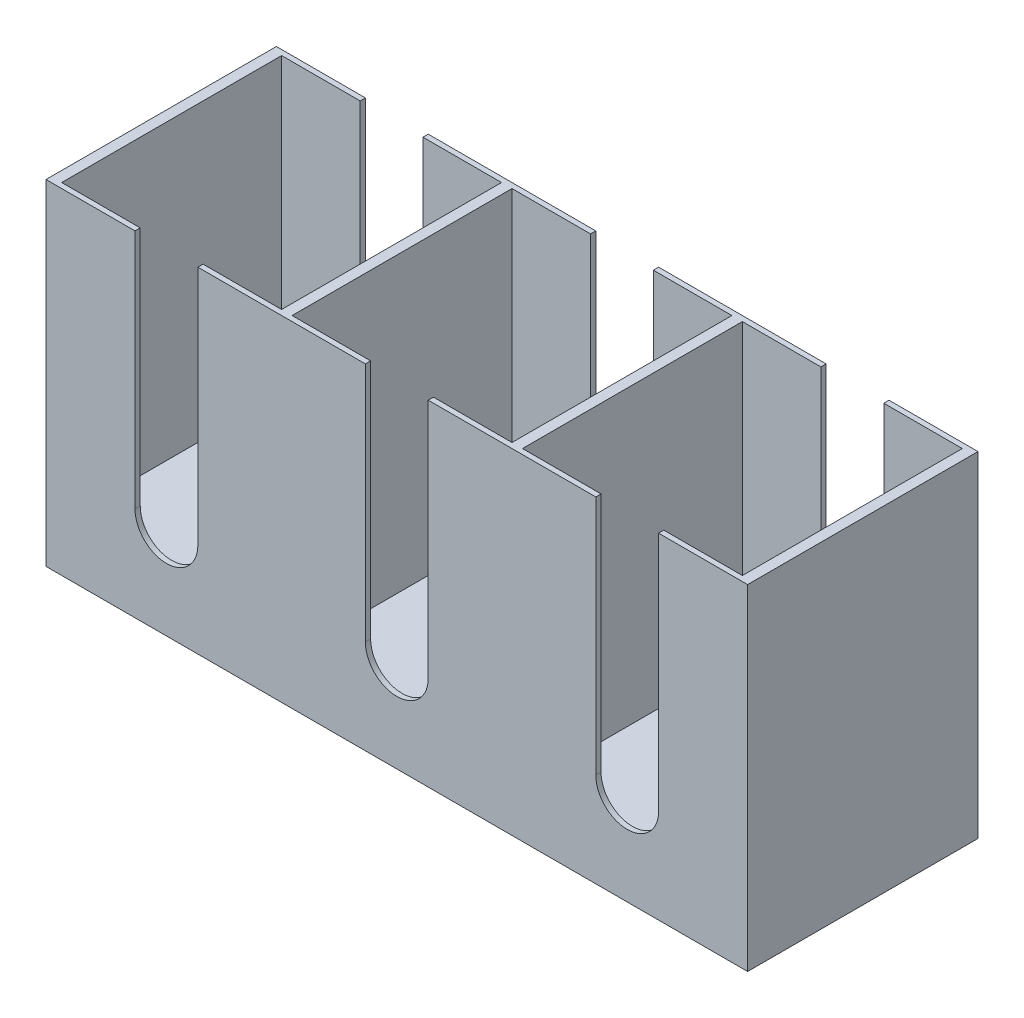
SolidWorks part; units mm, degrees
material "ABS"
ref_plane "Alzado" through (0, 0, 0) normal (0, 0, 1) x (1, 0, 0)
ref_plane "Planta" through (0, 0, 0) normal (0, 1, 0) x (1, 0, 0)
ref_plane "Vista lateral" through (0, 0, 0) normal (1, 0, 0) x (0, 0, -1)
sketch "Croquis1" plane through (0, 0, 0) normal (0, 1, 0) x (1, 0, 0)
  line L0 (-10.5, 10.5) -> (10.5, 10.5)
  line L1 (-33.5, 11) -> (33.5, 11)
  line L2 (-33.5, 11) -> (-33.5, -11)
  line L3 (-33.5, -11) -> (33.5, -11)
  line L4 (33.5, 11) -> (33.5, -11)
  line L5 (-33.5, 11) -> (33.5, -11) construction
  line L6 (-33.5, -11) -> (33.5, 11) construction
  line L11 (-10.5, 10.5) -> (-10.5, -10.5)
  line L12 (10.5, 10.5) -> (10.5, -10.5)
  line L13 (-32.5, 10.5) -> (-11.5, 10.5)
  line L14 (-32.5, 10.5) -> (-32.5, -10.5)
  line L15 (-32.5, -10.5) -> (-11.5, -10.5)
  line L16 (-11.5, 10.5) -> (-11.5, -10.5)
  line L17 (-32.5, 10.5) -> (-11.5, -10.5) construction
  line L18 (-32.5, -10.5) -> (-11.5, 10.5) construction
  line L19 (-10.5, -10.5) -> (10.5, -10.5)
  line L20 (11.5, 10.5) -> (32.5, 10.5)
  line L21 (11.5, 10.5) -> (11.5, -10.5)
  line L22 (32.5, 10.5) -> (32.5, -10.5)
  line L23 (11.5, -10.5) -> (32.5, -10.5)
  point P0 (0, 0)
  point P5 (0, 0)
  point P13 (-22, 0)
  dimension "D1" = 22
  dimension "D2" = 67
  dimension "D3" = 3
  dimension "D4" = 21
  dimension "D5" = 1
  dimension "D6" = 1
extrude "Saliente-Extruir1" add sketch "Croquis1" along normal blind 32
extrude "Saliente-Extruir2" add sketch "Croquis1<2>" along normal blind 4 contours L11 L19 L12 L0 | L16 L13 L14 L15 | L21 L23 L22 L20 region at (0, 0, 0) region at (-22, 0, 0) region at (22, 0, 0)
sketch "Croquis1<2>" plane through (0, 0, 0) normal (0, 1, 0) x (1, 0, 0) same geometry as "Croquis1"
sketch "Croquis2" plane through (0, 0, 11) normal (0, 0, 1) x (1, 0, 0)
  line L0 (-25, 32) -> (-25, 9)
  line L1 (-33.5, 32) -> (33.5, 32) construction
  line L2 (-19, 9) -> (-19, 32)
  line L3 (-19, 32) -> (-25, 32)
  line L5 (-33.5, 32) -> (-33.5, 0) construction
  line L6 (-33.5, 0) -> (33.5, 0) construction
  line L7 (-3, 32) -> (-3, 9)
  line L8 (3, 32) -> (-3, 32)
  line L9 (3, 9) -> (3, 32)
  line L10 (19, 32) -> (19, 9)
  line L11 (25, 32) -> (19, 32)
  line L12 (25, 9) -> (25, 32)
  line L14 (33.5, 32) -> (33.5, 0) construction
  arc A0 (-25, 9) -> (-19, 9) centre (-22, 9) ccw
  arc A1 (-3, 9) -> (3, 9) centre (0, 9) ccw
  arc A2 (19, 9) -> (25, 9) centre (22, 9) ccw
  dimension "D1" = 6
  dimension "D3" = 9
  dimension "D2" = 11.5
  dimension "D5" = 11.5
  dimension "D4" = 3
extrude "Cortar-Extruir1" cut sketch "Croquis2" against normal through all
